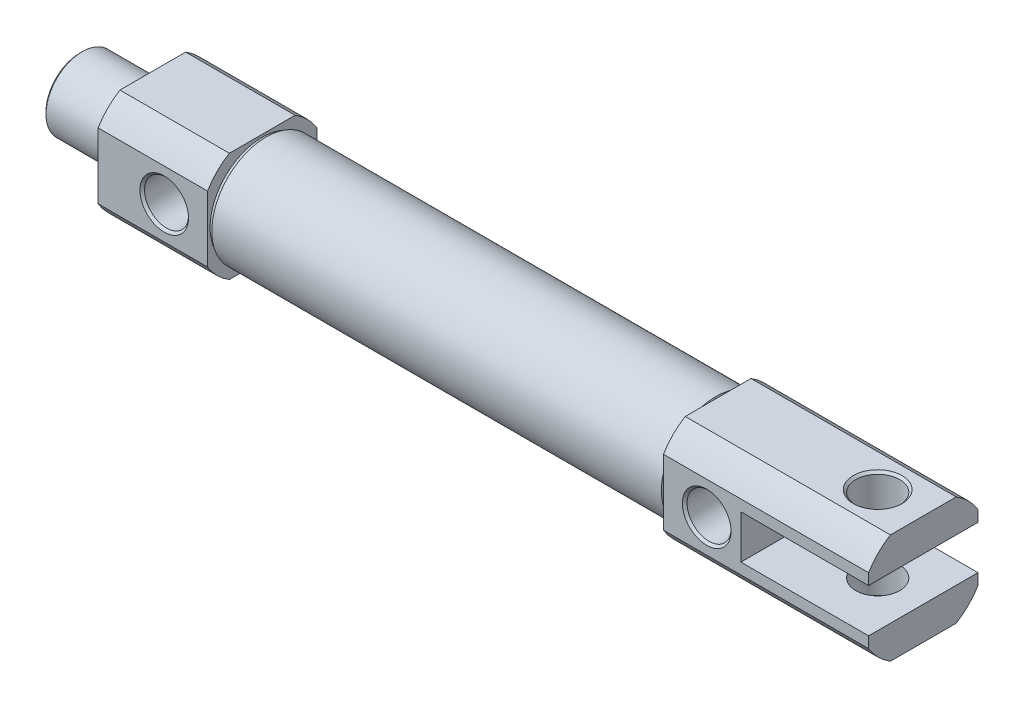
SolidWorks part; units mm, degrees
ref_plane "Front Plane" through (0, 0, 0) normal (0, 0, 1) x (1, 0, 0)
ref_plane "Top Plane" through (0, 0, 0) normal (0, 1, 0) x (1, 0, 0)
ref_plane "Right Plane" through (0, 0, 0) normal (1, 0, 0) x (0, 0, -1)
sketch "Sketch1" plane through (0, 0, 0) normal (1, 0, 0) x (0, 0, -1)
  circle A0 centre (0, 0) radius 5
  circle A1 centre (0, 0) radius 5.97
  dimension "D1" = 10
  dimension "D2" = 11.94
extrude "Boss-Extrude1" add sketch "Sketch1" along normal mid plane 30.4 contours A0 region at (0, 0, 0)
extrude "Boss-Extrude2" add sketch "Sketch1<3>" along normal mid plane 50
sketch "Sketch1<3>" plane through (0, 0, 0) normal (1, 0, 0) x (0, 0, -1) same geometry as "Sketch1"
chamfer "Chamfer1" distance 0.254 angle 60 1 edges at (25, 0, -5.97) first distance on face at (25, 0, -5.97)
chamfer "Chamfer2" distance 0.254 angle 60 1 edges at (-25, 0, -5.97) first distance on face at (-25, 0, -5.97)
sketch "Sketch2" plane through (25, 0, 0) normal (1, 0, 0) x (0, 0, -1)
  line L1 (6, -6) -> (-6, -6)
  line L2 (6, -6) -> (6, 6)
  line L3 (6, 6) -> (-6, 6)
  line L4 (-6, -6) -> (-6, 6)
  line L5 (6, -6) -> (-6, 6) construction
  line L6 (6, 6) -> (-6, -6) construction
  circle A0 centre (0, 0) radius 7
  point P0 (0, 0)
  dimension "D3" = 14
  dimension "D1" = 12
  dimension "D2" = 12
sketch "Sketch3" plane through (25, 0, 0) normal (1, 0, 0) x (0, 0, -1)
  line L0 (-6, 3.6055) -> (-6, -3.6055)
  line L1 (6, 3.6055) -> (6, -3.6055)
  line L2 (-3.6055, 6) -> (3.6055, 6)
  line L3 (-3.6055, -6) -> (3.6055, -6)
  line L4 (6, -6) -> (6, 6) construction
  line L5 (6, 6) -> (-6, 6) construction
  line L6 (-6, -6) -> (-6, 6) construction
  line L7 (6, -6) -> (-6, -6) construction
  arc A0 (-6, 3.6055) -> (-3.6055, 6) centre (0, 0) cw
  arc A1 (6, 3.6055) -> (3.6055, 6) centre (0, 0) ccw
  arc A2 (6, -3.6055) -> (3.6055, -6) centre (0, 0) cw
  arc A3 (-6, -3.6055) -> (-3.6055, -6) centre (0, 0) ccw
  circle A4 centre (0, 0) radius 7 construction
extrude "Boss-Extrude3" add sketch "Sketch3" along normal blind 22.5
sketch "Sketch5" plane through (0, 6, 0) normal (0, 1, 0) x (1, 0, 0)
  line L0 (47.5, 3.6055) -> (47.5, -3.6055) construction
  circle A0 centre (42.5, 0) radius 2.415
  dimension "D2" = 4.8301
  dimension "D1" = 5
extrude "Cut-Extrude2" cut sketch "Sketch5" against normal through all
sketch "Sketch6" plane through (0, 0, 6) normal (0, 0, 1) x (1, 0, 0)
  line L0 (47.5, 3.6055) -> (47.5, -3.6055) construction
  line L1 (33.5, -2.39) -> (47.5, -2.39)
  line L2 (33.5, -2.39) -> (33.5, 2.39)
  line L3 (33.5, 2.39) -> (47.5, 2.39)
  line L4 (47.5, -2.39) -> (47.5, 2.39)
  line L5 (33.5, -2.39) -> (47.5, 2.39) construction
  line L6 (33.5, 2.39) -> (47.5, -2.39) construction
  point P0 (40.5, 0)
  dimension "D1" = 14
  dimension "D2" = 4.78
extrude "Cut-Extrude3" cut sketch "Sketch6" against normal through all
extrude "Boss-Extrude4" add sketch "Sketch3<2>" against normal blind 12 from surface starting at face at (-25, 0, -5.716)
sketch "Sketch3<2>" plane through (25, 0, 0) normal (1, 0, 0) x (0, 0, -1) same geometry as "Sketch3"
sketch "Sketch4" plane through (0, 0, 6) normal (0, 0, 1) x (1, 0, 0)
  line L0 (25, 3.6055) -> (25, -3.6055) construction
  line L1 (-25, 3.6055) -> (-25, -3.6055) construction
  circle A0 centre (29.75, 0) radius 2.415
  circle A1 centre (-29.75, 0) radius 2.415
  dimension "D2" = 4.8301
  dimension "D1" = 4.75
  dimension "D3" = 4.75
extrude "Cut-Extrude4" cut sketch "Sketch4" against normal blind 6
sketch "Sketch8" plane through (-37, 0, 0) normal (-1, 0, 0) x (0, 0, 1)
  circle A0 centre (0, 0) radius 3.9688
  circle A1 centre (0, 0) radius 2.1827
  dimension "D1" = 4.3655
  dimension "D2" = 7.9375
extrude "Boss-Extrude5" add sketch "Sketch8" along normal blind 8
chamfer "Chamfer5" distance 0.254 angle 45 6 edges at (42.5, -6, 2.415) (42.5, 6, 2.415) (32.165, 0, 6) (-27.335, 0, 6) (-45, 0, 3.9688) (-45, 0, 2.1827)
equation "\"D2@Sketch2\"=\"D1@Sketch2\""
